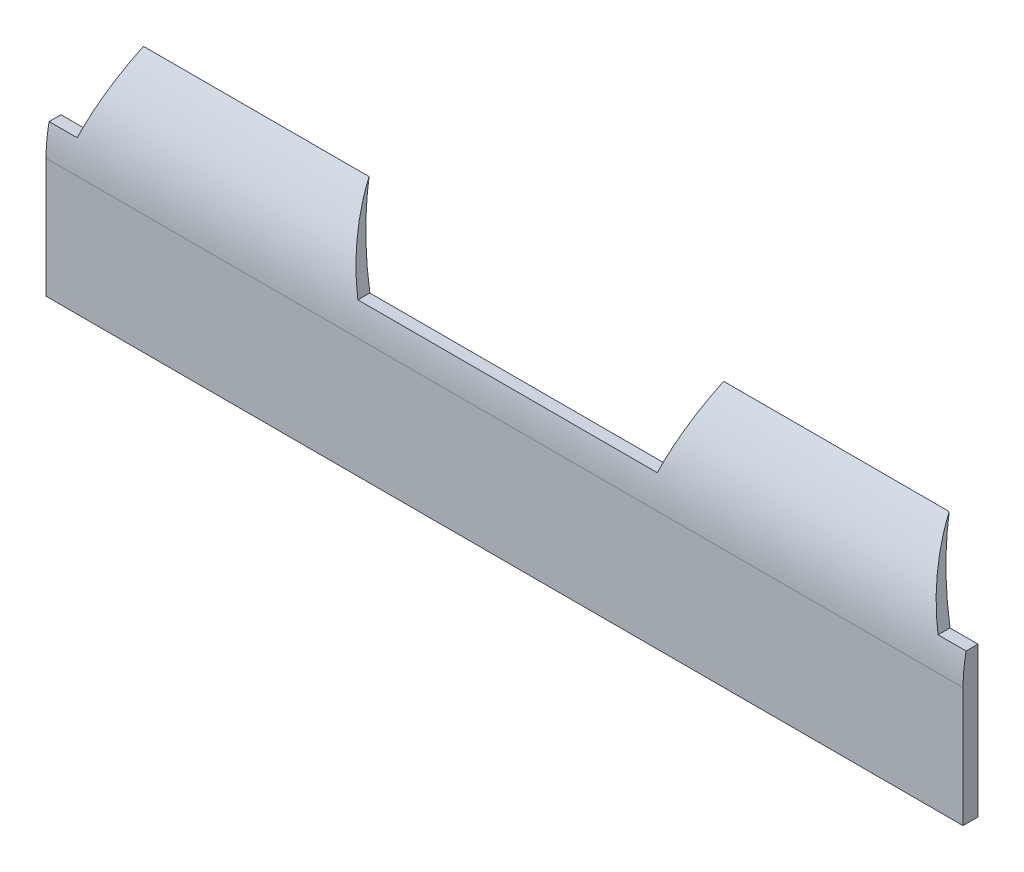
SolidWorks part; units mm, degrees
ref_plane "Přední rovina" through (0, 0, 0) normal (0, 0, 1) x (1, 0, 0)
ref_plane "Horní rovina" through (0, 0, 0) normal (0, 1, 0) x (1, 0, 0)
ref_plane "Pravá rovina" through (0, 0, 0) normal (1, 0, 0) x (0, 0, -1)
sketch "Skica1" plane through (0, 0, 0) normal (0, 0, 1) x (1, 0, 0)
  line L0 (0, 53.9152) -> (0, -0.2295) construction
  line L1 (24.5, -0.2295) -> (-24.5, -0.2295)
  line L2 (-24.5, -0.2295) -> (-24.5, 7.7705)
  line L3 (24.5, -0.2295) -> (24.5, 7.7705)
  line L4 (-24.5, 7.7705) -> (-23, 7.7705)
  line L5 (24.5, 7.7705) -> (23, 7.7705)
  line L6 (-23, 7.7705) -> (-21.5, 11.7705)
  line L7 (23, 7.7705) -> (21.5, 11.7705)
  line L8 (-21.5, 11.7705) -> (-9.5, 11.7705)
  line L9 (21.5, 11.7705) -> (9.5, 11.7705)
  line L10 (-9.5, 11.7705) -> (-8, 7.7705)
  line L11 (9.5, 11.7705) -> (8, 7.7705)
  line L12 (-8, 7.7705) -> (8, 7.7705)
  point P15 (0, 7.7705)
  dimension "D1" = 8
  dimension "D2" = 49
  dimension "D3" = 16
  dimension "D4" = 15
  dimension "D5" = 12
  dimension "D6" = 1.5
  dimension "D7" = 12
extrude "Přidat vysunutím2" add sketch "Skica1" along normal blind 0.8
sketch "Skica2" plane through (0, 0, 0) normal (0, 0, -1) x (-1, 0, 0)
  line L0 (-23, 7.7705) -> (-21.5, 11.7705)
  line L1 (-21.5, 11.7705) -> (-9.5, 11.7705)
  line L2 (-9.5, 11.7705) -> (-8, 7.7705)
  line L3 (-8, 7.7705) -> (-23, 7.7705)
  line L4 (8, 7.7705) -> (23, 7.7705)
  line L5 (23, 7.7705) -> (21.5, 11.7705)
  line L6 (21.5, 11.7705) -> (9.5, 11.7705)
  line L7 (9.5, 11.7705) -> (8, 7.7705)
extrude "Přidat vysunutím3" add sketch "Skica2" along normal blind 1.5
fillet "Zaoblit1" radius 8 1 edges at (15.5, 11.7705, 0.8)
ref_plane "Rovina1" through (24.5, 7.7705, 0) normal (0, 1, 0) x (1, 0, 0)
sketch "Skica7" plane through (24.5, 0, 0) normal (1, 0, 0) x (0, 0, -1)
  line L1 (0, 7.7399) -> (1.9482, 7.7399)
  line L2 (1.9482, 7.7399) -> (1.9482, 12.516)
  spline S0 degree 2 poles (0, 7.7399) (0.4733, 10.3751) (1.9482, 12.516) knots 0 0 0 1 1 1
extrude "Odebrat vysunutím3" cut sketch "Skica7" against normal through all
